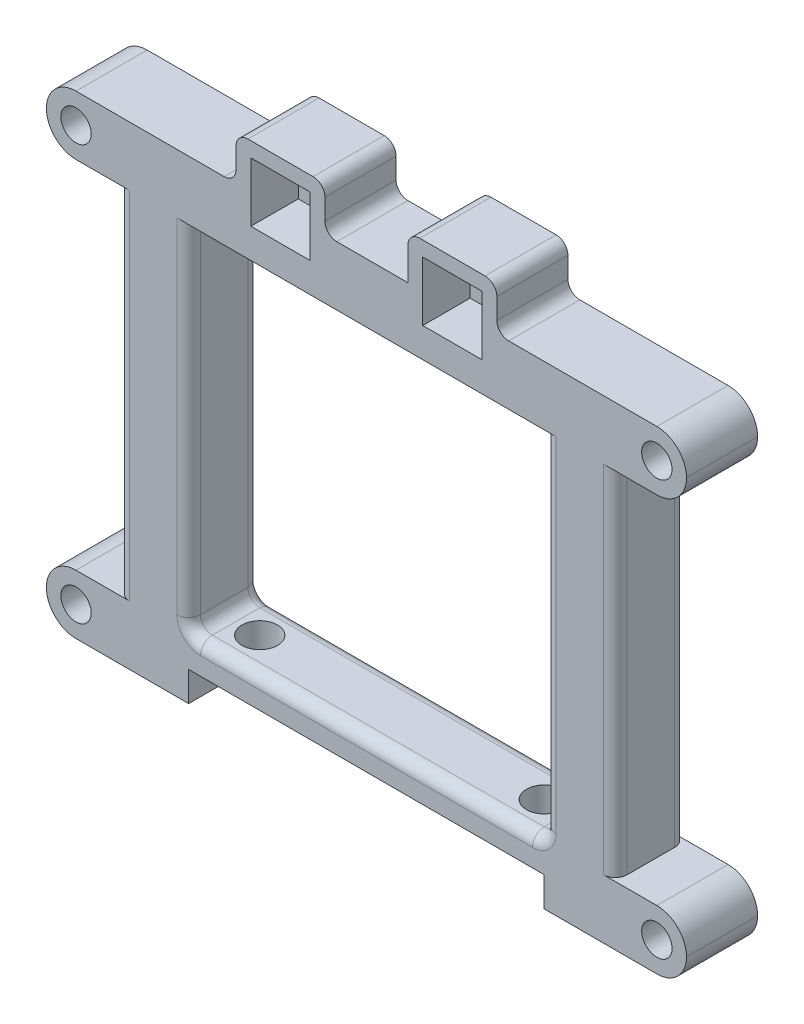
SolidWorks part; units mm, degrees
ref_plane "Front Plane" through (0, 0, 0) normal (0, 0, 1) x (1, 0, 0)
ref_plane "Top Plane" through (0, 0, 0) normal (0, 1, 0) x (1, 0, 0)
ref_plane "Right Plane" through (0, 0, 0) normal (1, 0, 0) x (0, 0, -1)
sketch "Sketch3" plane through (0, 0, 0) normal (0, 0, 1) x (1, 0, 0)
  line L0 (-26.67, 22.225) -> (0, 22.225) construction
  line L1 (34.29, -3.175) -> (-34.29, -3.175) construction
  line L2 (34.29, -3.175) -> (34.29, 3.175)
  line L3 (34.29, 3.175) -> (26.67, 3.175)
  line L4 (-34.29, -3.175) -> (-34.29, 3.175)
  line L5 (34.29, -3.175) -> (-34.29, 3.175) construction
  line L6 (34.29, 3.175) -> (-34.29, -3.175) construction
  line L8 (-26.67, 3.175) -> (-26.67, 41.275)
  line L10 (-19.05, 3.175) -> (-19.05, 41.275)
  line L11 (0, -55) -> (0, 55) construction
  line L12 (-26.67, 3.175) -> (-34.29, 3.175)
  line L13 (34.29, 47.625) -> (34.29, 41.275)
  line L14 (34.29, 47.625) -> (13.97, 47.625)
  line L15 (-34.29, 47.625) -> (-34.29, 41.275)
  line L16 (-26.67, 41.275) -> (-34.29, 41.275)
  line L17 (34.29, 41.275) -> (26.67, 41.275)
  line L18 (26.67, 3.175) -> (26.67, 41.275)
  line L19 (19.05, 3.175) -> (19.05, 41.275)
  line L20 (19.05, 41.275) -> (-19.05, 41.275)
  line L21 (19.05, 3.175) -> (-19.05, 3.175)
  line L24 (-19.05, -3.175) -> (-34.29, -3.175)
  line L26 (19.05, -3.175) -> (34.29, -3.175)
  line L27 (-19.05, 0) -> (19.05, 0)
  line L28 (-19.05, 0) -> (-19.05, -3.175)
  line L29 (19.05, 0) -> (19.05, -3.175)
  line L36 (19.05, 41.275) -> (19.05, 3.175) construction
  line L43 (-13.97, 47.625) -> (-34.29, 47.625)
  line L45 (-13.97, 47.625) -> (-13.97, 52.3875)
  line L46 (-13.97, 52.3875) -> (-4.445, 52.3875)
  line L47 (-4.445, 47.625) -> (-4.445, 52.3875)
  line L48 (4.445, 47.625) -> (4.445, 52.3875)
  line L49 (13.97, 47.625) -> (13.97, 52.3875)
  line L50 (13.97, 52.3875) -> (4.445, 52.3875)
  line L51 (4.445, 47.625) -> (-4.445, 47.625)
  point P0 (0, 0)
  dimension "D1" = 6.35
  dimension "D2" = 68.58
  dimension "D3" = 7.62
  dimension "D4" = 7.62
  dimension "D5" = 38.1
  dimension "D6" = 3.175
  dimension "D7" = 4.7625
  dimension "D8" = 5.08
  dimension "D9" = 9.525
extrude "Boss-Extrude2" add sketch "Sketch3" along normal mid plane 7.62
fillet "Fillet1" radius 3.175 8 edges at (34.29, 3.175, 0) (34.29, 41.275, 0) (34.29, 47.625, 0) (-34.29, 3.175, 0) (-34.29, 41.275, 0) (34.29, -3.175, 0) (-34.29, -3.175, 0) (-34.29, 47.625, 0)
sketch "Sketch4" plane through (0, 0, 3.81) normal (0, 0, 1) x (1, 0, 0)
  circle A0 centre (-31.115, 44.45) radius 1.627
  circle A1 centre (-31.115, 0) radius 1.627
  arc A2 (-34.29, 44.45) -> (-31.115, 41.275) centre (-31.115, 44.45) ccw construction
  dimension "D1" = 3.254
  dimension "D2" = 3.254
extrude "Cut-Extrude1" cut sketch "Sketch4" against normal up to next
mirror "Mirror1" about plane through (0, 0, 0) normal (1, 0, 0) of "Cut-Extrude1"
fillet "Fillet2" radius 1.27 19 edges at (0, 3.175, 3.81) (0, 3.175, -3.81) (19.05, 22.225, 3.81) (19.05, 3.175, 0) (19.05, 22.225, -3.81) (-19.05, 3.175, 0) (-19.05, 22.225, 3.81) (-19.05, 22.225, -3.81) (26.67, 22.225, 3.81) (26.67, 22.225, -3.81) (-26.67, 22.225, -3.81) (-26.67, 22.225, 3.81) (-13.97, 47.625, 0) (4.445, 52.3875, 0) (13.97, 47.625, 0) (13.97, 52.3875, 0) (-4.445, 47.625, 0) (-4.445, 52.3875, 0) (-13.97, 52.3875, 0)
sketch "Sketch5" plane through (0, 0, 0) normal (0, -1, 0) x (1, 0, 0)
  line L0 (0, 3.81) -> (0, -3.81) construction
  line L1 (-19.05, 3.81) -> (19.05, 3.81) construction
  line L2 (-19.05, -3.81) -> (19.05, -3.81) construction
  circle A0 centre (-15.24, 0) radius 1.905
  circle A1 centre (15.24, 0) radius 1.905
  dimension "D1" = 3.81
  dimension "D2" = 15.24
extrude "Cut-Extrude2" cut sketch "Sketch5" against normal up to next
sketch "Sketch7" plane through (0, 0, 3.81) normal (0, 0, 1) x (1, 0, 0)
  line L1 (-12.3825, 44.45) -> (-6.0325, 44.45)
  line L2 (-12.3825, 44.45) -> (-12.3825, 50.8)
  line L3 (-12.3825, 50.8) -> (-6.0325, 50.8)
  line L4 (-6.0325, 44.45) -> (-6.0325, 50.8)
  line L5 (-12.3825, 44.45) -> (-6.0325, 50.8) construction
  line L6 (-12.3825, 50.8) -> (-6.0325, 44.45) construction
  line L7 (-5.715, 52.3875) -> (-12.7, 52.3875) construction
  point P0 (-9.2075, 47.625)
  point P9 (-9.2075, 52.3875)
  point P10 (-6.0325, 47.625)
  dimension "D1" = 6.35
extrude "Cut-Extrude4" cut sketch "Sketch7" against normal blind 5.08
mirror "Mirror2" about plane through (0, 0, 0) normal (1, 0, 0) of "Cut-Extrude4"
